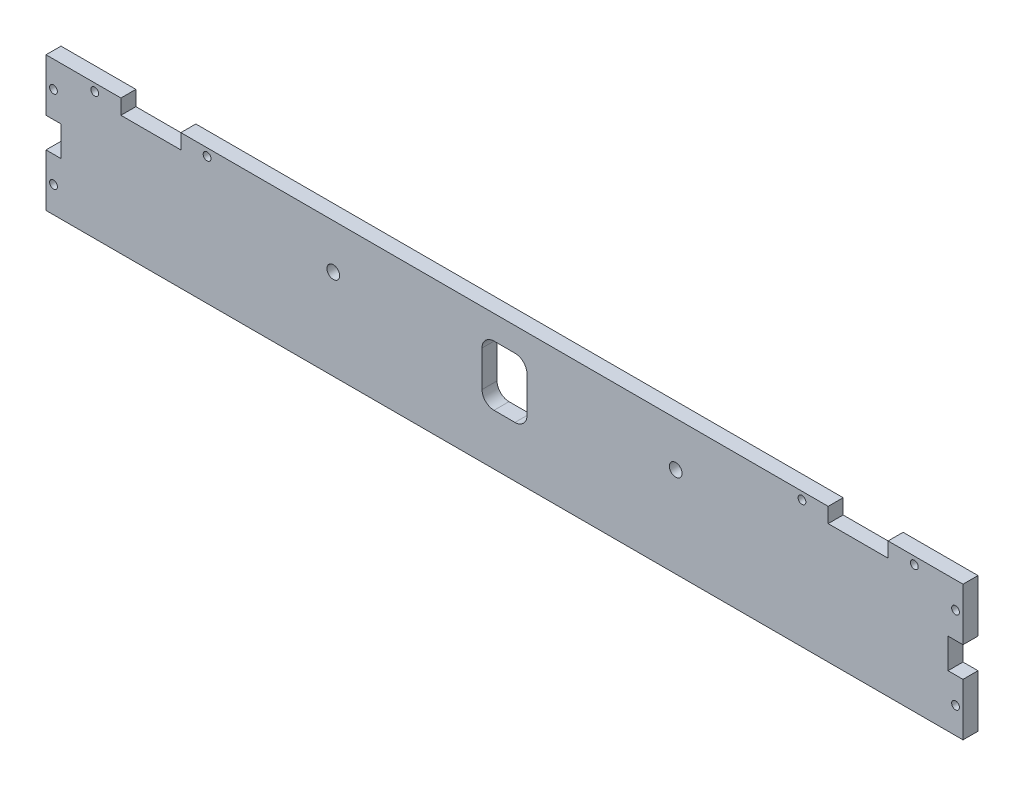
SolidWorks part; units mm, degrees
material "Pine"
ref_plane "Front Plane" through (0, 0, 0) normal (0, 0, 1) x (1, 0, 0)
ref_plane "Top Plane" through (0, 0, 0) normal (0, 1, 0) x (1, 0, 0)
ref_plane "Right Plane" through (0, 0, 0) normal (1, 0, 0) x (0, 0, -1)
ref_plane "Plane1" through (0, 0, 215.9) normal (0, 0, -1) x (-1, 0, 0)
sketch "Sketch1" plane through (0, 0, 215.9) normal (0, 0, -1) x (-1, 0, 0)
  line L0 (192.405, 21.59) -> (183.515, 21.59)
  line L1 (178.435, 26.67) -> (178.435, 41.91)
  line L2 (183.515, 46.99) -> (192.405, 46.99)
  line L3 (197.485, 41.91) -> (197.485, 26.67)
  line L4 (50.8, 57.15) -> (50.8, 50.8)
  line L5 (50.8, 50.8) -> (25.4, 50.8)
  line L6 (25.4, 50.8) -> (25.4, 57.15)
  line L7 (25.4, 57.15) -> (-6.35, 57.15)
  line L8 (-6.35, 57.15) -> (-6.35, 34.925)
  line L9 (-6.35, 34.925) -> (0, 34.925)
  line L10 (0, 34.925) -> (0, 22.225)
  line L11 (0, 22.225) -> (-6.35, 22.225)
  line L12 (-6.35, 22.225) -> (-6.35, 0)
  line L13 (-6.35, 0) -> (382.27, 0)
  line L14 (382.27, 0) -> (382.27, 22.225)
  line L15 (382.27, 22.225) -> (375.92, 22.225)
  line L16 (375.92, 22.225) -> (375.92, 34.925)
  line L17 (375.92, 34.925) -> (382.27, 34.925)
  line L18 (382.27, 34.925) -> (382.27, 57.15)
  line L19 (382.27, 57.15) -> (350.52, 57.15)
  line L20 (350.52, 57.15) -> (350.52, 50.8)
  line L21 (350.52, 50.8) -> (325.12, 50.8)
  line L22 (325.12, 50.8) -> (325.12, 57.15)
  line L23 (325.12, 57.15) -> (50.8, 57.15)
  circle A0 centre (379.095, 11.1125) radius 1.65
  circle A1 centre (-3.175, 11.1125) radius 1.65
  circle A2 centre (379.095, 46.0375) radius 1.65
  circle A3 centre (-3.175, 46.0375) radius 1.65
  arc A4 (183.515, 21.59) -> (178.435, 26.67) centre (183.515, 26.67) cw
  arc A5 (178.435, 41.91) -> (183.515, 46.99) centre (183.515, 41.91) cw
  arc A6 (192.405, 46.99) -> (197.485, 41.91) centre (192.405, 41.91) cw
  arc A7 (197.485, 26.67) -> (192.405, 21.59) centre (192.405, 26.67) cw
  circle A8 centre (314.0075, 53.975) radius 1.65
  circle A9 centre (61.9125, 53.975) radius 1.65
  circle A10 centre (361.6325, 53.975) radius 1.65
  circle A11 centre (14.2875, 53.975) radius 1.65
  circle A12 centre (260.51, 38.26) radius 2.7
  circle A13 centre (115.41, 38.26) radius 2.7
extrude "Boss-Extrude1" add sketch "Sketch1" against normal blind 6.35
